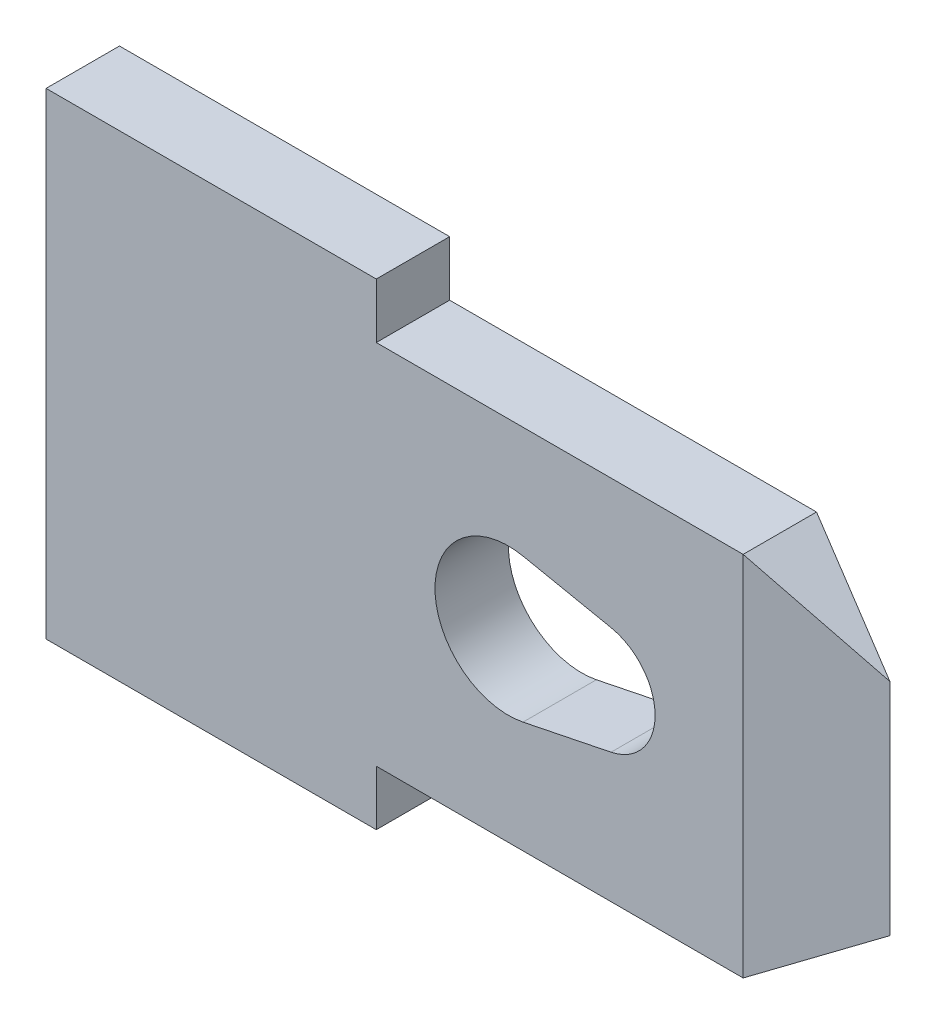
SolidWorks part; units mm, degrees
material "1.4301 (X5CrNi18-10)"
ref_plane "Płaszczyzna przednia" through (0, 0, 0) normal (0, 0, 1) x (1, 0, 0)
ref_plane "Płaszczyzna górna" through (0, 0, 0) normal (0, 1, 0) x (1, 0, 0)
ref_plane "Płaszczyzna prawa" through (0, 0, 0) normal (1, 0, 0) x (0, 0, -1)
sketch "Szkic1" plane through (0, 0, 0) normal (0, 0, 1) x (1, 0, 0)
  line L0 (0, 0) -> (11, 0) construction
  line L1 (0, -3.25) -> (0, 3.25)
  line L2 (0, 3.25) -> (4.5, 3.25)
  line L3 (4.5, 3.25) -> (4.5, 2.5)
  line L4 (4.5, 2.5) -> (9.5, 2.5)
  line L5 (9.5, 2.5) -> (11, 1.5)
  line L6 (11, 1.5) -> (11, -1.5)
  line L7 (9.5, -2.5) -> (11, -1.5)
  line L8 (4.5, -2.5) -> (9.5, -2.5)
  line L9 (4.5, -3.25) -> (4.5, -2.5)
  line L10 (0, -3.25) -> (4.5, -3.25)
  dimension "D1" = 11
  dimension "D2" = 6.5
  dimension "D3" = 5
  dimension "D4" = 3
  dimension "D5" = 4.5
  dimension "D6" = 5
extrude "Dodanie-wyciągnięcie1" add sketch "Szkic1" along normal blind 1
sketch "Szkic2" plane through (0, 0, 1) normal (0, 0, 1) x (1, 0, 0)
  line L0 (0, 0) -> (11, 0) construction
  line L1 (0, 3.25) -> (0, -3.25) construction
  line L2 (11, -1.5) -> (11, 1.5) construction
  line L3 (6.5, 0.9798) -> (7.7, 0.7348)
  line L4 (6.5, -0.9798) -> (7.7, -0.7348)
  arc A0 (6.5, 0.9798) -> (6.5, -0.9798) centre (6.3, 0) ccw
  arc A1 (7.7, -0.7348) -> (7.7, 0.7348) centre (7.55, 0) ccw
  dimension "D1" = 2
  dimension "D2" = 1.5
  dimension "D3" = 1.25
  dimension "D4" = 3.45
extrude "Wytnij-wyciągnięcie1" cut sketch "Szkic2" against normal up to next
sketch "Szkic3" plane through (0, 2.5, 0) normal (0, 1, 0) x (1, 0, 0)
  line L0 (11, -0.5) -> (9.5, 0)
  line L1 (11, -1) -> (11, 0) construction
  line L2 (9.5, 0) -> (9.5, -1) construction
  line L3 (9.5, -1) -> (11, -0.5)
  line L4 (9.5, 0) -> (11, 0)
  line L5 (11, 0) -> (11, -1)
  line L6 (11, -1) -> (9.5, -1)
extrude "Wytnij-wyciągnięcie2" cut sketch "Szkic3" against normal up to next contours L6 L5 L3 | L5 L4 L0 region at (10.5, 2.5, 0.8333) region at (10.5, 2.5, 0.1667)
